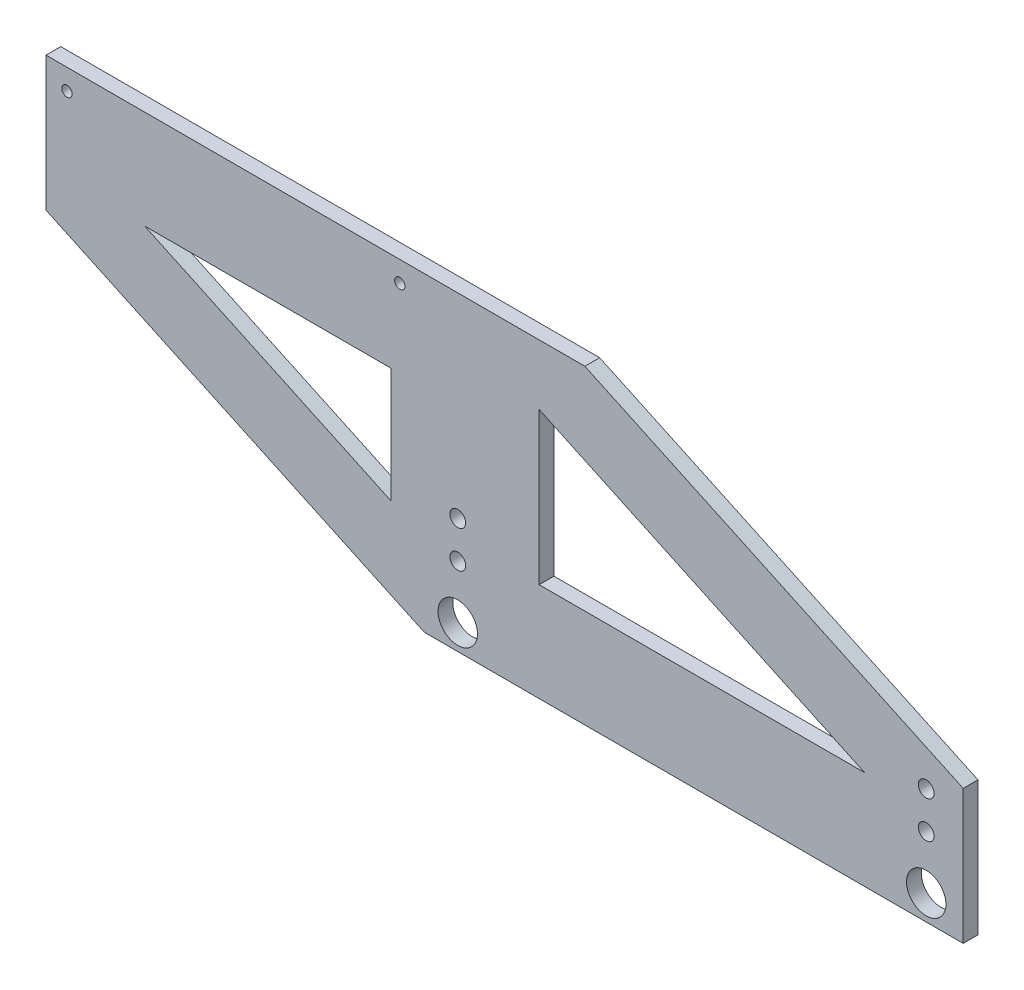
SolidWorks part; units mm, degrees
ref_plane "Front Plane" through (0, 0, 0) normal (0, 0, 1) x (1, 0, 0)
ref_plane "Top Plane" through (0, 0, 0) normal (0, 1, 0) x (1, 0, 0)
ref_plane "Right Plane" through (0, 0, 0) normal (1, 0, 0) x (0, 0, -1)
sketch "Sketch1" plane through (0, 0, 0) normal (0, 0, 1) x (1, 0, 0)
  line L0 (102.5, 14.1154) -> (102.5, 28.65) construction
  line L1 (-83.5, 74.1154) -> (25.7792, 74.1154)
  line L2 (-83.5, 74.1154) -> (-83.5, 46.8909)
  line L3 (-6.7792, 11.1154) -> (102.5, 11.1154)
  line L4 (102.5, 38.3399) -> (102.5, 11.1154)
  line L6 (-16.5, 11.1154) -> (-23.5, 11.1154) construction
  line L7 (-83.5, 71.1154) -> (-83.5, 14.1154) construction
  line L8 (-80.5, 74.1154) -> (-10.5, 74.1154) construction
  line L9 (25.7792, 74.1154) -> (102.5, 38.3399)
  line L10 (-83.5, 46.8909) -> (-6.7792, 11.1154)
  line L11 (-63.5, 54.1154) -> (-13.5, 54.1154)
  line L12 (-13.5, 54.1154) -> (-13.5, 30.8)
  line L13 (-13.5, 30.8) -> (-63.5, 54.1154)
  line L14 (16.5, 61.8917) -> (16.5, 31.1154)
  line L15 (16.5, 31.1154) -> (82.5, 31.1154)
  line L16 (82.5, 31.1154) -> (16.5, 61.8917)
  circle A0 centre (-79.25, 69.9154) radius 1.05
  circle A1 centre (-11.75, 69.9154) radius 1.05
  circle A2 centre (0, 16.2019) radius 4
  circle A3 centre (95, 16.2019) radius 4
  circle A4 centre (95, 27) radius 1.6
  circle A5 centre (95, 34.5) radius 1.6
  circle A6 centre (0, 34.5) radius 1.6
  circle A7 centre (0, 27) radius 1.6
  dimension "D1" = 3.2
  dimension "D2" = 8
  dimension "D3" = 2.1
  dimension "D4" = 115
  dimension "D5" = 15
  dimension "D6" = 15
  dimension "D7" = 20
  dimension "D8" = 20
  dimension "D9" = 50
  dimension "D10" = 20
  dimension "D11" = 30
extrude "Extrude1" add sketch "Sketch1" along normal blind 3
